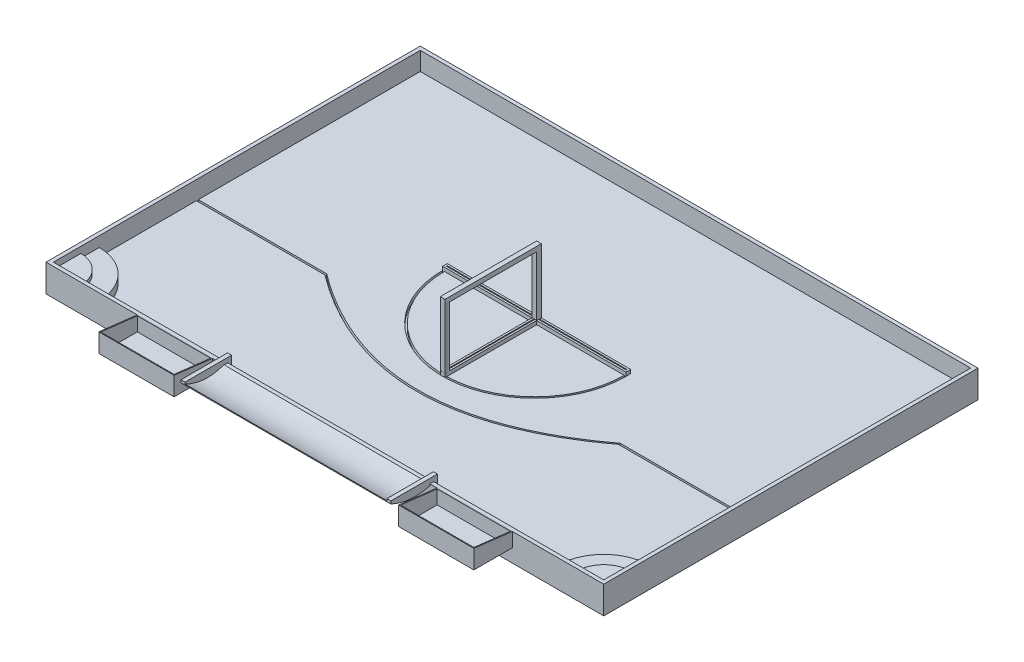
SolidWorks part; units mm, degrees
ref_plane "Plan de face" through (0, 0, 0) normal (0, 0, 1) x (1, 0, 0)
ref_plane "Plan de dessus" through (0, 0, 0) normal (0, 1, 0) x (1, 0, 0)
ref_plane "Plan de droite" through (0, 0, 0) normal (1, 0, 0) x (0, 0, -1)
sketch "Esquisse1" plane through (0, 0, 0) normal (0, 1, 0) x (1, 0, 0)
  line L1 (1520, 1020) -> (-1520, 1020)
  line L2 (1520, 1020) -> (1520, -1020)
  line L3 (1520, -1020) -> (-1520, -1020)
  line L4 (-1520, 1020) -> (-1520, -1020)
  line L5 (1520, 1020) -> (-1520, -1020) construction
  line L6 (1520, -1020) -> (-1520, 1020) construction
  point P0 (0, 0)
  dimension "D1" = 2040
  dimension "D2" = 3040
extrude "BASE TABLE" add sketch "Esquisse1" along normal blind 50
sketch "Esquisse2" plane through (0, 50, 0) normal (0, 1, 0) x (1, 0, 0)
  line L0 (-1520, -1020) -> (1520, -1020) construction
  line L1 (-1500, -210) -> (-1500, -220)
  line L2 (-1500, -220) -> (-800, -220)
  line L3 (-1520, 1020) -> (-1520, -1020) construction
  line L4 (800, -220) -> (1500, -220)
  line L5 (1520, -1020) -> (1520, 1020) construction
  line L6 (-1500, -210) -> (-800, -210)
  line L7 (800, -210) -> (1500, -210)
  line L8 (1500, -220) -> (1500, -210)
  spline S0 degree 2 poles (-800, -220) (0, -820) (800, -220) knots 0 0 0 1 1 1
  spline S1 degree 2 poles (-800, -210) (0, -810) (800, -210) knots 0 0 0 1 1 1
  point P0 (-800, -220)
  point P1 (0, -520)
  point P2 (800, -220)
  point P17 (0, -510)
  dimension "D1" = 800
  dimension "D2" = 500
  dimension "D3" = 800
  dimension "D4" = 800
  dimension "D5" = 800
  dimension "D6" = 0
  dimension "D7" = 20
  dimension "D8" = 20
  dimension "D9" = 10
  dimension "D10" = 10
  dimension "D11" = 10
extrude "LIGNE" cut sketch "Esquisse2" against normal blind 20
sketch "Esquisse3" plane through (0, 50, 0) normal (0, 1, 0) x (1, 0, 0)
  line L1 (1520, 1020) -> (-1520, 1020)
  line L2 (1520, 1020) -> (1520, -1020)
  line L3 (1520, -1020) -> (-1520, -1020)
  line L4 (-1520, 1020) -> (-1520, -1020)
  line L5 (1520, 1020) -> (-1520, -1020) construction
  line L6 (1520, -1020) -> (-1520, 1020) construction
  line L7 (1500, 1000) -> (-1500, 1000)
  line L8 (1500, 1000) -> (1500, -1000)
  line L9 (1500, -1000) -> (-1500, -1000)
  line L10 (-1500, 1000) -> (-1500, -1000)
  line L11 (1499.9999, 1006.5789) -> (-1499.9999, -1006.5789) construction
  line L12 (1500, -1006.5789) -> (-1500, 1006.5789) construction
  line L13 (1500, 1000) -> (-1500, -1000) construction
  line L14 (1500, -1000) -> (-1500, 1000) construction
  point P0 (0, 0)
  point P7 (0, 0)
  point P12 (0, 0)
  dimension "D1" = 20
  dimension "D2" = 20
extrude "EXT" add sketch "Esquisse3" along normal blind 100
sketch "Esquisse4" plane through (0, 50, 0) normal (0, 1, 0) x (1, 0, 0)
  line L0 (0, 493.526) -> (0, -1291.9694) construction
  line L1 (-1500, -750) -> (-1500, -1000)
  line L2 (-1500, -1000) -> (-1250, -1000)
  arc A0 (-1250, -1000) -> (-1500, -750) centre (-1500, -1000) ccw
  dimension "D1" = 500
extrude "COQ - BAS" add sketch "Esquisse4" along normal blind 44
ref_plane "PLAN DE SYMETRIE" through (0, 0, 0) normal (-1, 0, 0) x (0, 0, 1)
sketch "Esquisse7" plane through (0, 94, 0) normal (0, 1, 0) x (1, 0, 0)
  line L0 (-1500, -850) -> (-1500, -1000)
  line L1 (-1350, -1000) -> (-1500, -1000)
  arc A0 (-1350, -1000) -> (-1500, -850) centre (-1500, -1000) ccw
  dimension "D1" = 300
extrude "COQ - HAUT" add sketch "Esquisse7" along normal blind 22
mirror "SYM -COQ" about plane through (0, 0, 0) normal (-1, 0, 0) of "COQ - BAS", "COQ - HAUT"
sketch "Esquisse8" plane through (0, 150, 0) normal (0, 1, 0) x (1, 0, 0)
  line L0 (-1022, -1020) -> (-1022, -1230)
  line L1 (-1520, -1020) -> (1520, -1020) construction
  line L2 (-1022, -1230) -> (-612, -1230)
  line L3 (-612, -1230) -> (-612, -1020)
  line L4 (-612, -1020) -> (-1022, -1020)
  line L5 (-1022, -1020) -> (-1012.6073, -1017.8267)
  line L6 (-1520, 1020) -> (-1520, -1020) construction
  line L7 (-1022, -1020) -> (-612, -1230) construction
  line L9 (-617, -1025) -> (-1017, -1025)
  line L10 (-617, -1025) -> (-617, -1225)
  line L11 (-617, -1225) -> (-1017, -1225)
  line L12 (-1017, -1025) -> (-1017, -1225)
  line L13 (-617, -1025) -> (-1017, -1225) construction
  line L14 (-617, -1225) -> (-1017, -1025) construction
  point P9 (-817, -1125)
  line M8 (-1520, -1020) -> (1520, -1020)
  dimension "D1" = 498
  dimension "D2" = 410
  dimension "D3" = 210
  dimension "D4" = 5
  dimension "D5" = 5
extrude "POISSON EXT" add sketch "Esquisse8" against normal blind 75 and the other way blind 25 contours L2 L3 L0 L12 L9 L10 L11 M8 region at (-817, 150, 1024.6065)
sketch "Esquisse9" plane through (0, 75, 0) normal (0, -1, 0) x (1, 0, 0)
  line L0 (-1017, 1225) -> (-617, 1025) construction
  line L2 (-612, 1230) -> (-1022, 1230)
  line L3 (-612, 1230) -> (-612, 1020)
  line L4 (-612, 1020) -> (-1022, 1020)
  line L5 (-1022, 1230) -> (-1022, 1020)
  line L6 (-612, 1230) -> (-1022, 1020) construction
  line L7 (-612, 1020) -> (-1022, 1230) construction
  point P4 (-817, 1125)
extrude "POISSON FOND" add sketch "Esquisse9" along normal blind 2
sketch "Esquisse10" plane through (0, 50, 0) normal (0, 1, 0) x (1, 0, 0)
  line L0 (-500, 440) -> (-500, -316.5623) construction
  line L1 (500, 440) -> (500, -535.5421) construction
  line L2 (-593.2579, 121.8994) -> (656.1189, 121.8994) construction
  line L3 (0, 478.1315) -> (0, -280.8386) construction
  line L4 (-500, 121.8994) -> (-490, 121.8994)
  line L5 (490, 121.8994) -> (500, 121.8994)
  arc A0 (-500, 121.8994) -> (500, 121.8994) centre (0, 121.8994) ccw
  arc A1 (-490, 121.8994) -> (490, 121.8994) centre (0, 121.8994) ccw
  parabola Q2 (800, -210) -> (-800, -210) focus (0, 23.3333) apex (0, -510) construction
  point P0 (0, -378.1006)
  point P1 (-500, 440)
  point P2 (500, 440)
  point P7 (500, 440)
  point P11 (0, -528.1006)
  dimension "D7" = 10
  dimension "D1" = 150
  dimension "D2" = 300
  dimension "D3" = 300
  dimension "D4" = 650
  dimension "D5" = 650
  dimension "D6" = 331.8994
extrude "MILIEU VIDE" cut sketch "Esquisse10" against normal blind 20
sketch "Esquisse11" plane through (0, 50, 0) normal (0, 1, 0) x (1, 0, 0)
  line L0 (-500, 121.8994) -> (-12.5, 121.8994)
  line L1 (500, 121.8994) -> (500, 146.8994)
  line L2 (500, 146.8994) -> (-500, 146.8994)
  line L3 (-500, 146.8994) -> (-500, 121.8994)
  line L4 (-12.5, 121.8994) -> (-12.5, -367.9412)
  line L5 (12.5, 121.8994) -> (12.5, -367.9412)
  line L6 (-12.5, 121.8994) -> (12.5, -367.9412) construction
  line L7 (0, -123.0209) -> (0, 89.8409) construction
  line L8 (12.5, 121.8994) -> (500, 121.8994)
  arc A0 (-490, 121.8994) -> (490, 121.8994) centre (0, 121.8994) ccw construction
  arc A1 (-12.5, -367.7816) -> (12.5, -367.7816) centre (0, 121.8994) ccw
  dimension "D1" = 25
  dimension "D2" = 25
extrude "MILIEU BOIS " add sketch "Esquisse11" along normal blind 20 thin thin type one direction wall 10
sketch "Esquisse12" plane through (0, 70, 0) normal (0, 1, 0) x (1, 0, 0)
  line L0 (-12.7552, -377.7784) -> (-12.7552, -352.7784)
  line L2 (-12.7552, -377.7784) -> (12.7552, -377.7784)
  line L3 (-500, 146.8994) -> (500, 146.8994) construction
  line L4 (-12.7552, 146.8994) -> (12.7552, 146.8994)
  line L5 (12.7552, 146.8994) -> (12.7552, 121.8994)
  line L6 (12.7552, -377.7784) -> (-12.7552, -377.7784)
  line L7 (-12.5, 121.8994) -> (12.7552, 121.8994)
  line L8 (-12.7552, -352.7784) -> (12.7552, -352.7784)
  line L9 (12.7552, -352.7784) -> (12.7552, -377.7784)
  line L10 (-12.7552, 146.8994) -> (-12.5, 121.8994)
  line M1 (2.5, 131.8994) -> (2.5, -367.9348)
  arc M2 (2.5, -367.9348) -> (-2.5, -367.9348) centre (0, 121.8994) cw
  line M3 (-2.5, -367.9348) -> (-2.5, 131.8994)
  line M4 (-2.5, 131.8994) -> (-490, 131.8994)
  line M6 (-490, 136.8994) -> (490, 136.8994)
  line M8 (490, 131.8994) -> (2.5, 131.8994)
  line M9 (-12.5, 121.8994) -> (-12.5, -367.7816)
  line M10 (-12.5, -367.7816) -> (-12.7552, -377.7784)
  line M12 (12.7552, -377.7784) -> (12.5, -367.7816)
  line M13 (12.5, -367.7816) -> (12.5, 121.8994)
  line M14 (12.5, 121.8994) -> (500, 121.8994)
  line M16 (500, 146.8994) -> (-500, 146.8994)
  dimension "D1" = 25
extrude "MILIEU BOIS 2" add sketch "Esquisse12" along normal blind 350 contours L10 L7 M4 M3 | L10 L7 L5 M6 M4 M3 M1 M8 | L7 L5 M1 M14 M8 | L10 L5 M16 M6 | L8 M3 M2 M1 | L8 L2 M9 M10 M12 M13 M1 M2 M3 region at (-12.2705, 70, 372.7891) region at (0, 70, 360.3587) region at (-7.5256, 70, -126.9078) region at (0.0458, 70, -132.2803) region at (7.6276, 70, -126.8994) region at (0.0255, 70, -141.9027)
sketch "Esquisse13" plane through (0, 420, 0) normal (0, 1, 0) x (1, 0, 0)
  line L1 (12.7552, 146.8994) -> (-12.7552, 146.8994)
  line L2 (12.7552, 146.8994) -> (12.7552, -377.7784)
  line L3 (12.7552, -377.7784) -> (-12.7552, -377.7784)
  line L4 (-12.7552, 146.8994) -> (-12.7552, -377.7784)
extrude "MILIEU BOIS 3" add sketch "Esquisse13" against normal blind 25
sketch "Esquisse16" plane through (-1022, 0, 0) normal (-1, 0, 0) x (0, 0, 1)
  line L0 (1020, 150) -> (1230, 175)
  line L1 (1020, 150) -> (1239.9278, 153.4702) construction
  line L2 (1020, 150) -> (1020, 175)
  line L3 (1020, 175) -> (1230, 175)
extrude "Enlèv. mat.-Extru.1" cut sketch "Esquisse16" against normal blind 411 and the other way through all
ref_plane "PLAN FIXATION" through (-572, 0, 0) normal (1, 0, 0) x (0, 0, -1)
sketch "Esquisse17" plane through (1520, 0, 0) normal (1, 0, 0) x (0, 0, -1)
  line L2 (-1020, 150) -> (-1000, 150)
  line L3 (-1020, 150) -> (1020, 150) construction
  line L4 (-1000, 150) -> (-1000, 75)
  line L5 (-1000, 75) -> (-978, 75)
  line L6 (-978, 75) -> (-978, 175)
  line L7 (-978, 175) -> (-1232, 175)
  line L8 (-1232, 175) -> (-1232, 160)
  line L9 (-1020, 150) -> (-1020, 140)
  spline S0 degree 2 poles (-1232, 160) (-1126.8571, 111.9094) (-1020, 140) knots 0 0 0 1 1 1
  point P0 (-1084, 130)
  dimension "D1" = 254
  dimension "D2" = 100
  dimension "D3" = 10
  dimension "D4" = 15
  dimension "D5" = 148
  dimension "D6" = 45
  dimension "D7" = 22
  dimension "D8" = 20
sketch "Esquisse18" plane through (-572, 0, 0) normal (1, 0, 0) x (0, 0, -1)
  line L0 (-1020, 140) -> (-1020, 150)
  line L1 (-1020, 150) -> (-1000, 150)
  line L2 (-1000, 150) -> (-1000, 75)
  line L3 (-1000, 75) -> (-978, 75)
  line L4 (-978, 75) -> (-978, 175)
  line L5 (-1232, 160) -> (-1232, 175)
  line L6 (-1232, 175) -> (-978, 175)
  spline S0 degree 2 poles (-1232, 160) (-1126.8571, 111.9094) (-1020, 140) knots 0 0 0 1 1 1
extrude "Boss.-Extru.1" add sketch "Esquisse18" along normal blind 22
sketch "Esquisse20" plane through (-550, 0, 0) normal (1, 0, 0) x (0, 0, -1)
  line L1 (-1232, 165) -> (-1232, 160)
  line L2 (-1020, 150) -> (-1020, 0) construction
  line L3 (-1020, 150) -> (-1020, 73) construction
  line L4 (-1020, 140) -> (-1020, 150) construction
  line L5 (-1020, 150) -> (-1020, 145)
  parabola Q0 (-1232, 160) -> (-1020, 140) focus (-1101.9018, 277.6846) apex (-1105.2314, 129.717) construction
  spline S0 degree 2 poles (-1232, 160) (-1127.2656, 108.1555) (-1020, 145) knots 0 0 0 1 1 1
  spline S1 degree 2 poles (-1020, 150) (-1127.2656, 113.1555) (-1232, 165) knots 0 0 0 1 1 1
  dimension "D2" = 5
  dimension "D1" = 5
  dimension "D3" = 5
extrude "Boss.-Extru.2" add sketch "Esquisse20" along direction (-1, 0, 0) on the side of the normal up to surface (550 mm away) up to plane "PLAN DE SYMETRIE"
mirror "Symétrie1" about plane through (0, 0, 0) normal (-1, 0, 0) of "Enlèv. mat.-Extru.1", "POISSON FOND", "POISSON EXT", "Boss.-Extru.1", "Boss.-Extru.2"
ref_plane "Plan3" through (-1200, 0, 0) normal (1, 0, 0) x (0, 0, -1)
